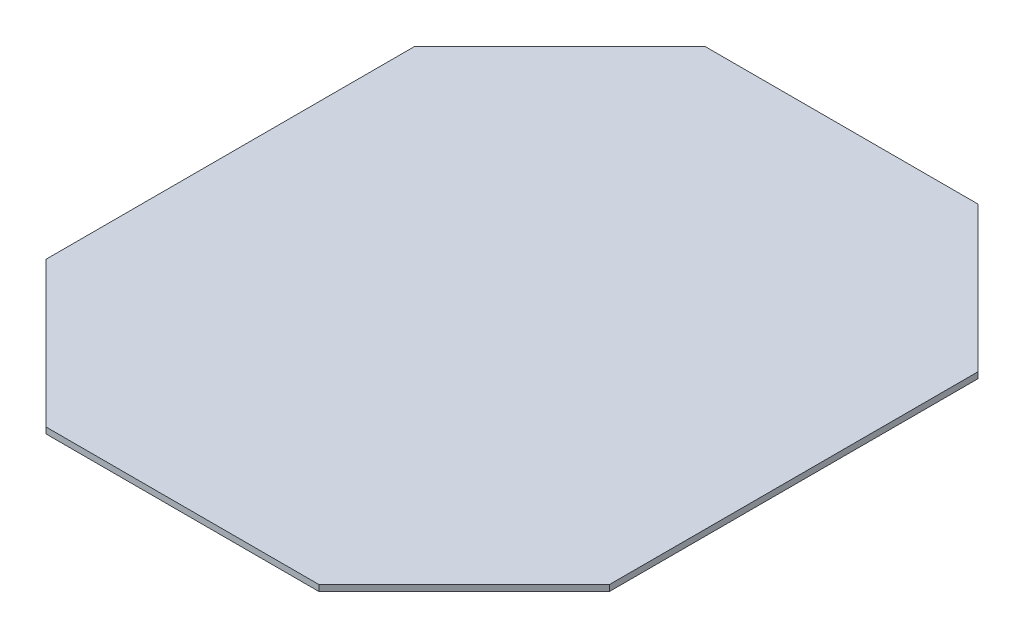
SolidWorks part; units mm, degrees
ref_plane "Front Plane" through (0, 0, 0) normal (0, 0, 1) x (1, 0, 0)
ref_plane "Top Plane" through (0, 0, 0) normal (0, 1, 0) x (1, 0, 0)
ref_plane "Right Plane" through (0, 0, 0) normal (1, 0, 0) x (0, 0, -1)
sketch "Sketch14" plane through (0, 0, 0) normal (0, 1, 0) x (1, 0, 0)
  line L1 (224, 92.7838) -> (92.7838, 224)
  line L2 (92.7838, 224) -> (-92.7838, 224)
  line L3 (-92.7838, 224) -> (-224, 92.7838)
  line L4 (-224, 92.7838) -> (-224, -92.7838)
  line L5 (-224, -92.7838) -> (-92.7838, -224)
  line L6 (-92.7838, -224) -> (92.7838, -224)
  line L7 (92.7838, -224) -> (224, -92.7838)
  line L8 (224, -92.7838) -> (224, 92.7838)
  circle A0 centre (0, 0) radius 224 construction
extrude "Boss-Extrude2" add sketch "Sketch14" along normal blind 4.12
sketch "Sketch16" plane through (0, 0, 0) normal (0, -1, 0) x (1, 0, 0)
  line L0 (-191.5, -224) -> (-191.5, 224)
  line L1 (-191.5, -224) -> (191.5, -224)
  line L2 (-191.5, 224) -> (191.5, 224)
  line L3 (191.5, -224) -> (191.5, 224)
  line L4 (-191.5, -224) -> (191.5, 224) construction
  line L5 (-191.5, 224) -> (191.5, -224) construction
  point P1 (0, 0)
  dimension "D1" = 383
ref_point "Point9"
ref_point "Point10"
sketch "Sketch17" plane through (0, 0, 0) normal (0, -1, 0) x (1, 0, 0)
  line L0 (191.5, 125.2838) -> (191.5, -125.742)
  line L1 (191.5, -125.742) -> (224, -92.7838)
  line L2 (224, -92.7838) -> (224, 92.7838)
  line L3 (224, 92.7838) -> (191.5, 125.2838)
extrude "Cut-Extrude2" cut sketch "Sketch17" against normal blind 4.12
ref_point "Point11"
ref_point "Point12"
sketch "Sketch18" plane through (0, 0, 0) normal (0, -1, 0) x (1, 0, 0)
  line L0 (-191.5, 125.2838) -> (-224, 92.7838)
  line L1 (-224, 92.7838) -> (-224, -92.7838)
  line L2 (-224, -92.7838) -> (-191.5, -125.2838)
  line L3 (-191.5, -125.2838) -> (-191.5, 125.2838)
extrude "Cut-Extrude3" cut sketch "Sketch18" against normal blind 4.12
